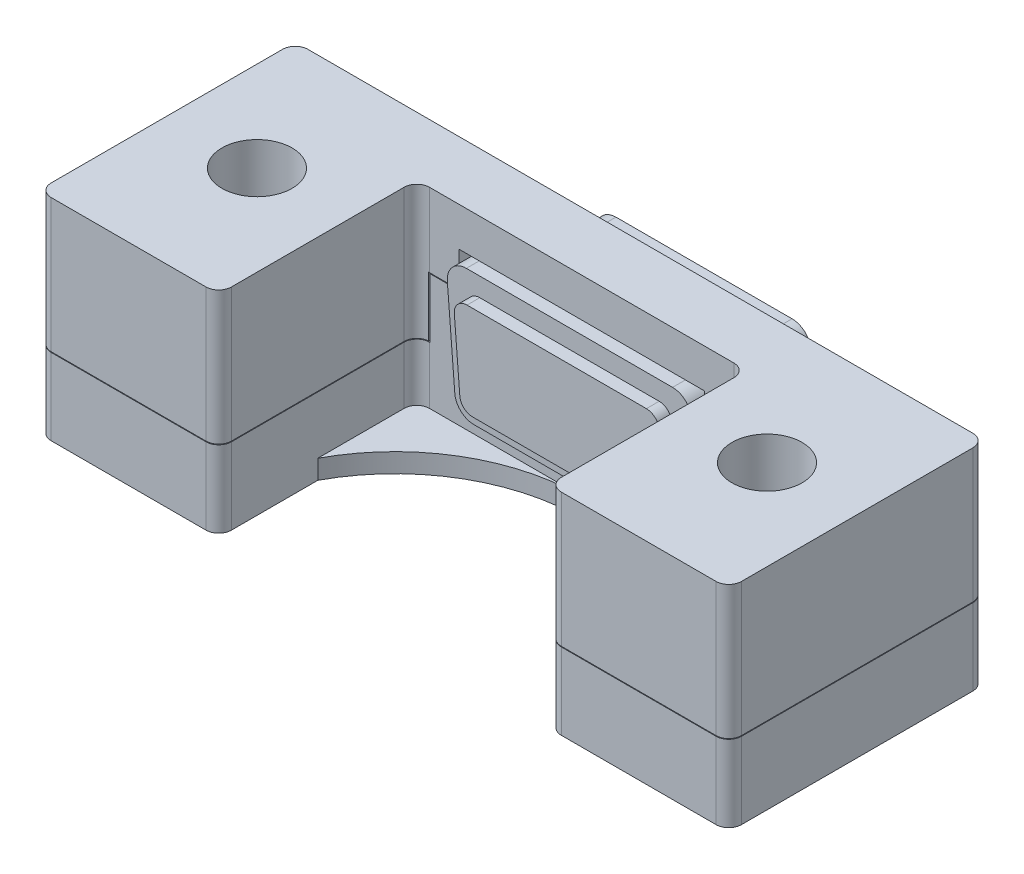
SolidWorks part; units mm, degrees
note: The reader was unsure of these and kept them because the rebuilt part matched: shared geometry of "Sketch1<3>", "Sketch12<2>".
other "DB9-F"
other "Mount-Top"
other "Mount-Bottom"
ref_plane "Front Plane" through (0, 0, 0) normal (0, 0, 1) x (1, 0, 0)
ref_plane "Top Plane" through (0, 0, 0) normal (0, 1, 0) x (1, 0, 0)
ref_plane "Right Plane" through (0, 0, 0) normal (1, 0, 0) x (0, 0, -1)
sketch "Sketch1" plane through (0, 0, 0) normal (0, 0, 1) x (1, 0, 0)
  line L0 (15.435, 12.52) -> (15.435, 0) construction
  line L1 (0, 0) -> (30.87, 0)
  line L2 (0, 0) -> (0, 12.52)
  line L3 (0, 12.52) -> (30.87, 12.52)
  line L4 (30.87, 0) -> (30.87, 12.52)
  line L5 (0, 6.26) -> (30.87, 6.26) construction
  line L6 (21.5467, 2.0833) -> (9.3233, 2.0833)
  line L7 (7.8409, 3.354) -> (7.0476, 8.484)
  line L8 (8.53, 10.2133) -> (22.34, 10.2133)
  line L9 (9.3233, 2.0833) -> (8.0374, 2.0833) construction
  line L10 (8.0374, 2.0833) -> (7.8409, 3.354) construction
  line L11 (7.0476, 8.484) -> (6.7802, 10.2133) construction
  line L12 (6.7802, 10.2133) -> (8.53, 10.2133) construction
  line L13 (7.03, 11.6158) -> (7.03, 8.7133) construction
  line L14 (24.0898, 10.2133) -> (22.34, 10.2133) construction
  line L15 (23.8224, 8.484) -> (24.0898, 10.2133) construction
  line L16 (22.8326, 2.0833) -> (23.0291, 3.354) construction
  line L17 (21.5467, 2.0833) -> (22.8326, 2.0833) construction
  line L18 (23.0291, 3.354) -> (23.8224, 8.484)
  circle A0 centre (2.92, 6.26) radius 1.5
  arc A1 (7.0476, 8.484) -> (8.53, 10.2133) centre (8.53, 8.7133) cw
  arc A2 (7.8409, 3.354) -> (9.3233, 2.0833) centre (9.3233, 3.5833) ccw
  arc A3 (23.0291, 3.354) -> (21.5467, 2.0833) centre (21.5467, 3.5833) cw
  arc A4 (23.8224, 8.484) -> (22.34, 10.2133) centre (22.34, 8.7133) ccw
  circle A5 centre (27.95, 6.26) radius 1.5
  point P11 (4.42, 6.26)
  point P12 (26.45, 6.26)
  point P16 (15.435, 2.0833)
  point P31 (15.435, 6.26)
  point P35 (15.435, 10.2133)
  dimension "D3" = 3
  dimension "D6" = 1.5
  dimension "D7" = 1.5
  dimension "D1" = 30.87
  dimension "D2" = 12.52
  dimension "D4" = 22.03
  dimension "D5" = 8.13
  dimension "D8" = 16.81
extrude "Boss-Extrude1" add sketch "Sketch1" along normal blind 0.64 contours L18 A4 L8 A1 L7 A2 L6 A3 | L1 L4 L3 L2 A0 A4 L18 A3 L6 A2 L7 A1 L8 A5
extrude "Boss-Extrude2" add sketch "Sketch1<3>" against normal blind 6 contours L18 A4 L8 A1 L7 A2 L6 A3
sketch "Sketch1<3>" plane through (0, 0, 0) normal (0, 0, 1) x (1, 0, 0) same geometry as "Sketch1"
sketch "Sketch2" plane through (0, 0, 0.64) normal (0, 0, 1) x (1, 0, 0)
  line L0 (15.435, 12.52) -> (15.435, 0) construction
  line L1 (22.9335, 1.1) -> (7.9365, 1.1)
  line L2 (6.4413, 2.4802) -> (5.8548, 9.8002)
  line L3 (7.35, 11.42) -> (23.52, 11.42)
  line L4 (7.9365, 1.1) -> (6.5519, 1.1) construction
  line L5 (6.5519, 1.1) -> (6.4413, 2.4802) construction
  line L6 (5.8548, 9.8002) -> (5.725, 11.42) construction
  line L7 (5.725, 11.42) -> (7.35, 11.42) construction
  line L8 (5.85, 12.8226) -> (5.85, 9.92) construction
  line L9 (25.145, 11.42) -> (23.52, 11.42) construction
  line L10 (25.0152, 9.8002) -> (25.145, 11.42) construction
  line L11 (24.3181, 1.1) -> (24.4287, 2.4802) construction
  line L12 (22.9335, 1.1) -> (24.3181, 1.1) construction
  line L13 (24.4287, 2.4802) -> (25.0152, 9.8002)
  line L14 (0, 12.52) -> (30.87, 12.52) construction
  line L15 (0, 0) -> (30.87, 0) construction
  arc A0 (5.8548, 9.8002) -> (7.35, 11.42) centre (7.35, 9.92) cw
  arc A1 (6.4413, 2.4802) -> (7.9365, 1.1) centre (7.9365, 2.6) ccw
  arc A2 (24.4287, 2.4802) -> (22.9335, 1.1) centre (22.9335, 2.6) cw
  arc A3 (25.0152, 9.8002) -> (23.52, 11.42) centre (23.52, 9.92) ccw
  point P6 (15.435, 1.1)
  point P20 (15.435, 6.26)
  point P22 (15.435, 11.42)
  point P23 (15.435, 12.52)
  point P24 (15.435, 0)
  point P29 (22.7031, 2.4336)
  point P30 (22.9766, 2.4889)
  dimension "D2" = 1.5
  dimension "D3" = 1.5
  dimension "D1" = 1.1
  dimension "D4" = 19.17
  dimension "D5" = 1.1
extrude "Boss-Extrude3" add sketch "Sketch2" along normal blind 3.91
sketch "Sketch3" plane through (0, 0, 4.55) normal (0, 0, 1) x (1, 0, 0)
  line L0 (7.9365, 1.1) -> (22.9335, 1.1) construction
  line L1 (24.4287, 2.4802) -> (25.0152, 9.8002) construction
  line L2 (23.52, 11.42) -> (7.35, 11.42) construction
  line L3 (5.8548, 9.8002) -> (6.4413, 2.4802) construction
  line L4 (7.9365, 1.1) -> (22.9335, 1.1)
  line L5 (24.4287, 2.4802) -> (25.0152, 9.8002)
  line L6 (23.52, 11.42) -> (7.35, 11.42)
  line L7 (5.8548, 9.8002) -> (6.4413, 2.4802)
  line L8 (8.8319, 2.57) -> (22.0381, 2.57)
  line L9 (23.0349, 3.4901) -> (23.466, 8.8701)
  line L10 (22.4692, 9.95) -> (8.4008, 9.95)
  line L11 (7.404, 8.8701) -> (7.8351, 3.4901)
  line L12 (15.435, 2.57) -> (15.435, 9.95) construction
  line L13 (7.9365, 2.57) -> (8.8319, 2.57) construction
  line L14 (7.9365, 2.57) -> (22.9335, 2.57) construction
  line L15 (7.8351, 3.4901) -> (7.9066, 2.5976) construction
  line L16 (7.3201, 9.9176) -> (7.9066, 2.5976) construction
  line L17 (7.3201, 9.9176) -> (7.404, 8.8701) construction
  line L18 (8.4008, 9.95) -> (7.35, 9.95) construction
  line L19 (23.52, 9.95) -> (7.35, 9.95) construction
  line L20 (23.52, 9.95) -> (22.4692, 9.95) construction
  line L21 (23.466, 8.8701) -> (23.5499, 9.9176) construction
  line L22 (22.9634, 2.5976) -> (23.5499, 9.9176) construction
  line L23 (22.0381, 2.57) -> (22.9335, 2.57) construction
  line L24 (22.9634, 2.5976) -> (23.0349, 3.4901) construction
  arc A0 (22.9335, 1.1) -> (24.4287, 2.4802) centre (22.9335, 2.6) ccw construction
  arc A1 (25.0152, 9.8002) -> (23.52, 11.42) centre (23.52, 9.92) ccw construction
  arc A2 (7.35, 11.42) -> (5.8548, 9.8002) centre (7.35, 9.92) ccw construction
  arc A3 (6.4413, 2.4802) -> (7.9365, 1.1) centre (7.9365, 2.6) ccw construction
  arc A4 (22.9335, 1.1) -> (24.4287, 2.4802) centre (22.9335, 2.6) ccw
  arc A5 (25.0152, 9.8002) -> (23.52, 11.42) centre (23.52, 9.92) ccw
  arc A6 (7.35, 11.42) -> (5.8548, 9.8002) centre (7.35, 9.92) ccw
  arc A7 (6.4413, 2.4802) -> (7.9365, 1.1) centre (7.9365, 2.6) ccw
  arc A8 (22.9335, 2.57) -> (22.9634, 2.5976) centre (22.9335, 2.6) ccw
  arc A9 (23.5499, 9.9176) -> (23.52, 9.95) centre (23.52, 9.92) ccw
  arc A10 (7.35, 9.95) -> (7.3201, 9.9176) centre (7.35, 9.92) ccw
  arc A11 (7.9066, 2.5976) -> (7.9365, 2.57) centre (7.9365, 2.6) ccw
  arc A12 (7.404, 8.8701) -> (8.4008, 9.95) centre (8.4008, 8.95) cw
  arc A13 (7.8351, 3.4901) -> (8.8319, 2.57) centre (8.8319, 3.57) ccw
  arc A14 (23.0349, 3.4901) -> (22.0381, 2.57) centre (22.0381, 3.57) cw
  arc A15 (23.466, 8.8701) -> (22.4692, 9.95) centre (22.4692, 8.95) ccw
  dimension "D2" = 1
  dimension "D3" = 5.3972
  dimension "D4" = 1
  dimension "D1" = 1.47
extrude "Boss-Extrude4" add sketch "Sketch3" along normal blind 1 contours L11 A11 L8 A8 L9 A9 L10 A10
sketch "Sketch4" plane through (0, 0, -6) normal (0, 0, -1) x (-1, 0, 0)
  line L0 (-7.8409, 3.354) -> (-7.0476, 8.484) construction
  line L1 (-21.5467, 2.0833) -> (-9.3233, 2.0833) construction
  line L2 (-23.0291, 3.354) -> (-23.8224, 8.484) construction
  line L3 (-8.53, 10.2133) -> (-22.34, 10.2133) construction
  line L4 (-7.8409, 3.354) -> (-7.0476, 8.484)
  line L5 (-21.5467, 2.0833) -> (-9.3233, 2.0833)
  line L6 (-23.0291, 3.354) -> (-23.8224, 8.484)
  line L7 (-8.53, 10.2133) -> (-22.34, 10.2133)
  line L8 (-8.0385, 3.3846) -> (-7.2453, 8.5146)
  line L9 (-8.53, 10.0133) -> (-22.34, 10.0133)
  line L10 (-22.8315, 3.3846) -> (-23.6247, 8.5146)
  line L11 (-21.5467, 2.2833) -> (-9.3233, 2.2833)
  arc A0 (-7.0476, 8.484) -> (-8.53, 10.2133) centre (-8.53, 8.7133) ccw construction
  arc A1 (-9.3233, 2.0833) -> (-7.8409, 3.354) centre (-9.3233, 3.5833) ccw construction
  arc A2 (-23.0291, 3.354) -> (-21.5467, 2.0833) centre (-21.5467, 3.5833) ccw construction
  arc A3 (-22.34, 10.2133) -> (-23.8224, 8.484) centre (-22.34, 8.7133) ccw construction
  arc A4 (-7.0476, 8.484) -> (-8.53, 10.2133) centre (-8.53, 8.7133) ccw
  arc A5 (-9.3233, 2.0833) -> (-7.8409, 3.354) centre (-9.3233, 3.5833) ccw
  arc A6 (-23.0291, 3.354) -> (-21.5467, 2.0833) centre (-21.5467, 3.5833) ccw
  arc A7 (-22.34, 10.2133) -> (-23.8224, 8.484) centre (-22.34, 8.7133) ccw
  arc A8 (-7.2453, 8.5146) -> (-8.53, 10.0133) centre (-8.53, 8.7133) ccw
  arc A9 (-22.34, 10.0133) -> (-23.6247, 8.5146) centre (-22.34, 8.7133) ccw
  arc A10 (-22.8315, 3.3846) -> (-21.5467, 2.2833) centre (-21.5467, 3.5833) ccw
  arc A11 (-9.3233, 2.2833) -> (-8.0385, 3.3846) centre (-9.3233, 3.5833) ccw
  dimension "D1" = 0.2
extrude "Cut-Extrude1" cut sketch "Sketch4" against normal blind 0.1 contours L11 A11 L8 A8 L9 A9 L10 A10
sketch "Sketch5" plane through (0, 0, 0) normal (0, 0, -1) x (-1, 0, 0)
  line L0 (-21.5467, 2.0833) -> (-9.3233, 2.0833) construction
  line L1 (-7.8409, 3.354) -> (-7.0476, 8.484) construction
  line L2 (-8.53, 10.2133) -> (-22.34, 10.2133) construction
  line L3 (-23.0291, 3.354) -> (-23.8224, 8.484) construction
  line L4 (-21.5467, 2.0833) -> (-9.3233, 2.0833) construction
  line L5 (-7.8409, 3.354) -> (-7.0476, 8.484) construction
  line L6 (-8.53, 10.2133) -> (-22.34, 10.2133) construction
  line L7 (-23.0291, 3.354) -> (-23.8224, 8.484) construction
  line L8 (-21.5467, 1.0833) -> (-9.3233, 1.0833)
  line L9 (-6.8526, 3.2012) -> (-6.0594, 8.3312)
  line L10 (-8.53, 11.2133) -> (-22.34, 11.2133)
  line L11 (-24.0174, 3.2012) -> (-24.8106, 8.3312)
  line L12 (0, 0) -> (0, 12.52) construction
  line L13 (-32.87, -2) -> (2, -2)
  line L14 (-32.87, -2) -> (-32.87, 14.52)
  line L15 (-32.87, 14.52) -> (2, 14.52)
  line L16 (2, -2) -> (2, 14.52)
  line L17 (0, 12.52) -> (-30.87, 12.52) construction
  line L18 (0, 4.4358) -> (2, 4.4358) construction
  line L19 (-9.7314, 0) -> (-9.7314, -2) construction
  line L20 (0, 0) -> (-30.87, 0) construction
  line L21 (-32.87, 1.7427) -> (-30.87, 1.7427) construction
  line L22 (-30.87, 0) -> (-30.87, 12.52) construction
  line L23 (-24.0174, 12.52) -> (-24.0174, 14.52) construction
  arc A0 (-9.3233, 2.0833) -> (-7.8409, 3.354) centre (-9.3233, 3.5833) ccw construction
  arc A1 (-7.0476, 8.484) -> (-8.53, 10.2133) centre (-8.53, 8.7133) ccw construction
  arc A2 (-22.34, 10.2133) -> (-23.8224, 8.484) centre (-22.34, 8.7133) ccw construction
  arc A3 (-23.0291, 3.354) -> (-21.5467, 2.0833) centre (-21.5467, 3.5833) ccw construction
  arc A4 (-9.3233, 2.0833) -> (-7.8409, 3.354) centre (-9.3233, 3.5833) ccw construction
  arc A5 (-7.0476, 8.484) -> (-8.53, 10.2133) centre (-8.53, 8.7133) ccw construction
  arc A6 (-22.34, 10.2133) -> (-23.8224, 8.484) centre (-22.34, 8.7133) ccw construction
  arc A7 (-23.0291, 3.354) -> (-21.5467, 2.0833) centre (-21.5467, 3.5833) ccw construction
  arc A8 (-9.3233, 1.0833) -> (-6.8526, 3.2012) centre (-9.3233, 3.5833) ccw
  arc A9 (-6.0594, 8.3312) -> (-8.53, 11.2133) centre (-8.53, 8.7133) ccw
  arc A10 (-22.34, 11.2133) -> (-24.8106, 8.3312) centre (-22.34, 8.7133) ccw
  arc A11 (-24.0174, 3.2012) -> (-21.5467, 1.0833) centre (-21.5467, 3.5833) ccw
  dimension "D2" = 2
  dimension "D1" = 1
extrude "Boss-Extrude5" add sketch "Sketch5" along normal blind 1 from offset 0.01 separate body
sketch "Sketch6" plane through (0, 0, -0.01) normal (0, 0, 1) x (1, 0, 0)
  line L0 (15.435, 14.52) -> (15.435, -2) construction
  line L1 (-2, 14.52) -> (32.87, 14.52) construction
  line L2 (32.87, -2) -> (-2, -2) construction
  line L3 (-0.05, 12.57) -> (30.92, 12.57)
  line L4 (30.92, 12.57) -> (30.92, -0.05)
  line L5 (30.92, -0.05) -> (-0.05, -0.05)
  line L6 (27.8294, -0.05) -> (27.8294, 0) construction
  line L7 (0, 0) -> (30.87, 0) construction
  line L8 (30.87, 2.0624) -> (30.92, 2.0624) construction
  line L9 (30.87, 0) -> (30.87, 12.52) construction
  line L10 (27.2415, 12.57) -> (27.2415, 12.52) construction
  line L11 (0, 12.52) -> (30.87, 12.52) construction
  line L12 (3.6285, 12.57) -> (3.6285, 12.52) construction
  line L13 (0, 2.0624) -> (-0.05, 2.0624) construction
  line L14 (3.0406, -0.05) -> (3.0406, 0) construction
  line L15 (-0.05, 12.57) -> (-0.05, -0.05)
  line L17 (-2, -2) -> (32.87, -2)
  line L18 (-2, -2) -> (-2, 14.52)
  line L19 (-2, 14.52) -> (32.87, 14.52)
  line L20 (32.87, -2) -> (32.87, 14.52)
  point P29 (15.435, -0.05)
  point P30 (15.435, 12.57)
  dimension "D1" = 0.05
extrude "Boss-Extrude6" add sketch "Sketch6" along normal blind 1.1
sketch "Sketch7" plane through (0, 0, 0.64) normal (0, 0, 1) x (1, 0, 0)
  circle A0 centre (2.92, 6.26) radius 1.9202
  circle A1 centre (27.95, 6.26) radius 1.8016
  circle A2 centre (27.95, 6.26) radius 1.5 construction
  circle A3 centre (2.92, 6.26) radius 1.5 construction
  circle A4 centre (27.95, 6.26) radius 1.5
  circle A5 centre (2.92, 6.26) radius 1.5
extrude "Boss-Extrude7" add sketch "Sketch7" along normal blind 0.44
sketch "Sketch8" plane through (0, 0, 0.64) normal (0, 0, 1) x (1, 0, 0)
  line L0 (15.435, 14.52) -> (15.435, -2) construction
  line L1 (32.87, 14.52) -> (-2, 14.52) construction
  line L2 (-2, -2) -> (32.87, -2) construction
  line L3 (25.07, 11.47) -> (5.8, 11.47)
  line L4 (5.8, 11.47) -> (5.8, 1.05)
  line L5 (5.8, 1.05) -> (25.07, 1.05)
  line L6 (5.85, 9.92) -> (5.85, 11.1529) construction
  line L7 (9.4755, 1.05) -> (9.4755, 1.1) construction
  line L8 (7.9365, 1.1) -> (22.9335, 1.1) construction
  line L9 (9.541, 11.42) -> (9.541, 11.47) construction
  line L10 (23.52, 11.42) -> (7.35, 11.42) construction
  line L11 (21.329, 11.42) -> (21.329, 11.47) construction
  line L12 (21.3945, 1.05) -> (21.3945, 1.1) construction
  line L13 (25.02, 9.92) -> (25.02, 11.1529) construction
  line L14 (25.07, 11.47) -> (25.07, 1.05)
  line L16 (-2, -2) -> (32.87, -2)
  line L17 (-2, -2) -> (-2, 14.52)
  line L18 (-2, 14.52) -> (32.87, 14.52)
  line L19 (32.87, -2) -> (32.87, 14.52)
  arc A0 (7.35, 11.42) -> (5.8548, 9.8002) centre (7.35, 9.92) ccw construction
  point P30 (15.435, 1.05)
  point P31 (15.435, 11.47)
  dimension "D1" = 0.05
  dimension "D2" = 0.05
extrude "Boss-Extrude8" add sketch "Sketch8" along normal blind 2.5 from offset 0.45
sketch "Sketch9" plane through (0, -2, 0) normal (0, -1, 0) x (1, 0, 0)
  line L0 (15.435, -1.01) -> (15.435, 25.9037) construction
  line L1 (32.87, -1.01) -> (-2, -1.01) construction
  line L3 (-4.565, 9.057) -> (-6.632, 9.057) construction
  line L4 (42.502, -1.01) -> (32.87, -1.01)
  line L5 (15.435, -1.01) -> (15.435, 19.124) construction
  line L6 (42.502, 19.124) -> (28.368, 19.124)
  line L7 (-11.632, -1.01) -> (-11.632, 19.124)
  line L8 (-4.565, 9.057) -> (-4.565, 11.124) construction
  line L9 (-4.565, 9.057) -> (-4.565, 6.99) construction
  line L10 (35.435, 9.057) -> (35.435, 6.99) construction
  line L11 (35.435, 9.057) -> (35.435, 11.124) construction
  line L12 (35.435, 9.057) -> (37.502, 9.057) construction
  line L13 (42.502, -1.01) -> (42.502, 19.124)
  line L14 (-2, -1.01) -> (15.435, -1.01) construction
  line L15 (15.435, -1.01) -> (32.87, -1.01) construction
  line L16 (-2, -1.01) -> (-2, 3.59)
  line L17 (-2, 3.59) -> (2.502, 3.59)
  line L18 (32.87, -1.01) -> (32.87, 3.59)
  line L19 (15.435, -1.01) -> (-2, -1.01) construction
  line L20 (-2, -1.01) -> (-11.632, -1.01)
  line L21 (32.87, -1.01) -> (15.435, -1.01) construction
  line L22 (2.502, 3.59) -> (2.502, 19.124)
  line L23 (-4.565, 9.057) -> (-2.498, 9.057) construction
  line L24 (28.368, 3.59) -> (28.368, 19.124)
  line L25 (2.502, 3.59) -> (15.435, 3.59) construction
  line L26 (28.368, 3.59) -> (32.87, 3.59)
  line L27 (15.435, 19.124) -> (2.502, 19.124) construction
  line L28 (2.502, 19.124) -> (-11.632, 19.124)
  line L29 (28.368, 19.124) -> (15.435, 19.124) construction
  line L30 (15.435, 3.59) -> (28.368, 3.59) construction
  circle A0 centre (-4.565, 9.057) radius 2.067
  circle A1 centre (35.435, 9.057) radius 2.067
  dimension "D1" = 4.134
  dimension "D2" = 40
  dimension "D3" = 8
  dimension "D4" = 8
  dimension "D5" = 5
  dimension "D6" = 5
extrude "Boss-Extrude10" add sketch "Sketch9" against normal up to surface (16.52 mm away) contours L7 L6 L13 L4 L18 L17 L16 L20 up to face at (15.435, 14.52, 1.29)
fillet "Fillet1" radius 1 8 edges at (42.502, 6.26, 19.124) (42.502, 6.26, -1.01) (-11.632, 6.26, -1.01) (-11.632, 6.26, 19.124) (2.502, 6.26, 19.124) (28.368, 6.26, 19.124) (28.368, 6.26, 3.59) (2.502, 6.26, 3.59)
sketch "Sketch10" plane through (0, -2, 0) normal (0, -1, 0) x (1, 0, 0)
  line L0 (15.435, 3.59) -> (15.435, 18.6364) construction
  line L1 (3.502, 3.59) -> (27.368, 3.59) construction
  line L2 (2.502, 4.59) -> (2.502, 18.124) construction
  line L3 (29.7841, 3.59) -> (1.0859, 3.59)
  line L4 (1.0859, 3.59) -> (1.0859, 11.357)
  line L5 (1.0859, 11.357) -> (2.502, 11.357)
  line L6 (29.7841, 11.357) -> (28.368, 11.357)
  line L7 (29.7841, 3.59) -> (29.7841, 11.357)
  arc A0 (2.502, 11.357) -> (28.368, 11.357) centre (15.435, 18.241) ccw
  line M5 (28.368, 18.124) -> (28.368, 4.59)
  arc M6 (28.368, 4.59) -> (27.368, 3.59) centre (27.368, 4.59) cw
  line M7 (27.368, 3.59) -> (3.502, 3.59)
  arc M8 (3.502, 3.59) -> (2.502, 4.59) centre (3.502, 4.59) cw
  line M9 (2.502, 4.59) -> (2.502, 18.124)
extrude "Boss-Extrude11" add sketch "Sketch10" against normal blind 1.5 contours A0 L3 M9 M8 | A0 M7 M6 M5
sketch "Sketch11" plane through (0, 0, -1.01) normal (0, 0, -1) x (-1, 0, 0)
  line L0 (10.632, 14.52) -> (-41.502, 14.52) construction
  line L1 (-27.435, 8.72) -> (-3.435, 8.72)
  line L2 (-27.435, 8.72) -> (-27.435, 8.67)
  line L3 (-27.335, 8.67) -> (-3.535, 8.67)
  line L4 (-3.435, 8.72) -> (-3.435, 8.67)
  line L5 (-15.435, 8.72) -> (-15.435, 14.52) construction
  line L6 (-27.435, 8.67) -> (-27.435, 4.05)
  line L7 (-27.335, 8.67) -> (-27.335, 4)
  line L8 (-27.335, 4) -> (-49.335, 4)
  line L9 (-49.335, 4) -> (-49.335, 4.05)
  line L10 (-49.335, 4.05) -> (-27.435, 4.05)
  line L11 (-41.502, -2) -> (10.632, -2) construction
  line L13 (18.465, 4.05) -> (-3.435, 4.05)
  line L14 (18.465, 4) -> (18.465, 4.05)
  line L15 (-3.535, 4) -> (18.465, 4)
  line L16 (-3.535, 8.67) -> (-3.535, 4)
  line L17 (-3.435, 8.67) -> (-3.435, 4.05)
  line L18 (-3.435, 8.72) -> (-3.435, 8.67)
  line M6 (-41.502, 14.52) -> (-41.502, -2)
  line M8 (10.632, -2) -> (10.632, 14.52)
  arc M11 (-24.8106, 8.3312) -> (-22.34, 11.2133) centre (-22.34, 8.7133) cw
  arc M13 (-8.53, 11.2133) -> (-6.0594, 8.3312) centre (-8.53, 8.7133) cw
  dimension "D1" = 5.8
  dimension "D2" = 0.05
  dimension "D3" = 24
  dimension "D4" = 0.1
  dimension "D5" = 0.05
  dimension "D6" = 6
extrude "Cut-Extrude2" cut sketch "Sketch11" against normal through all both and the other way through all contours L10 L8 L7 L3 L1 L2 L6 M6 M11 | L17 L4 L1 L3 L16 L15 L13 M13 M8 | L15 L14 L13 M8 | L10 L9 L8 M6
sketch "Sketch12" plane through (0, -2, 0) normal (0, -1, 0) x (1, 0, 0)
  line L0 (15.435, -1.01) -> (15.435, 23.7666) construction
  line L1 (41.502, -1.01) -> (-10.632, -1.01) construction
  circle A0 centre (-4.565, 9.057) radius 2.75
  circle A1 centre (35.435, 9.057) radius 2.75
  dimension "D1" = 5.5
extrude "Cut-Extrude3" cut sketch "Sketch12" against normal through all both and the other way through all
extrude "Cut-Extrude4" cut sketch "Sketch12<2>" along normal blind 5 and the other way through all from surface at -16.52 starting at face at (15.435, 14.52, 10.207)
sketch "Sketch12<2>" plane through (0, -2, 0) normal (0, -1, 0) x (1, 0, 0) same geometry as "Sketch12"
thread "Thread1" pitch 0.8 start angle 0, offset 1, length 7, pitch 0.8, diameter 4.134
ref_plane "Plane2" through (33.368, 10.52, 9.057) normal (0, 0, 1) x (-1, 0, 0)
sketch "Thread Profile2" plane through (33.368, 10.52, 9.057) normal (0, 0, 1) x (-1, 0, 0)
  line L0 (0, 0) -> (0, 0.8) construction
  line L1 (0, 0) -> (0.433, 0.25)
  line L2 (0.433, 0.25) -> (0.433, 0.35)
  line L3 (0.433, 0.35) -> (0, 0.6)
  line L4 (0.433, 0.3) -> (0, 0.3) construction
  line L11 (0, 0) -> (0, 0.6)
  point P2 (0, 0)
  dimension "Pitch" = 0.8
  dimension "Profile_Angle" = 60
  dimension "Profile_Land" = 0.1
  dimension "Profile_Height" = 0.433
thread "Thread2" pitch 0.8 profile "Thread Profile3" start angle 0, offset 1, length 7, pitch 0.8, diameter 4.134
ref_plane "Plane3" through (-6.632, 10.52, 9.057) normal (0, 0, 1) x (-1, 0, 0)
sketch "Thread Profile3" plane through (-6.632, 10.52, 9.057) normal (0, 0, 1) x (-1, 0, 0)
  line L0 (0, 0) -> (0, 0.8) construction
  line L1 (0, 0) -> (0.433, 0.25)
  line L2 (0.433, 0.25) -> (0.433, 0.35)
  line L3 (0.433, 0.35) -> (0, 0.6)
  line L4 (0.433, 0.3) -> (0, 0.3) construction
  line L11 (0, 0) -> (0, 0.6)
  point P2 (0, 0)
  dimension "Pitch" = 0.8
  dimension "Profile_Angle" = 60
  dimension "Profile_Land" = 0.1
  dimension "Profile_Height" = 0.433
